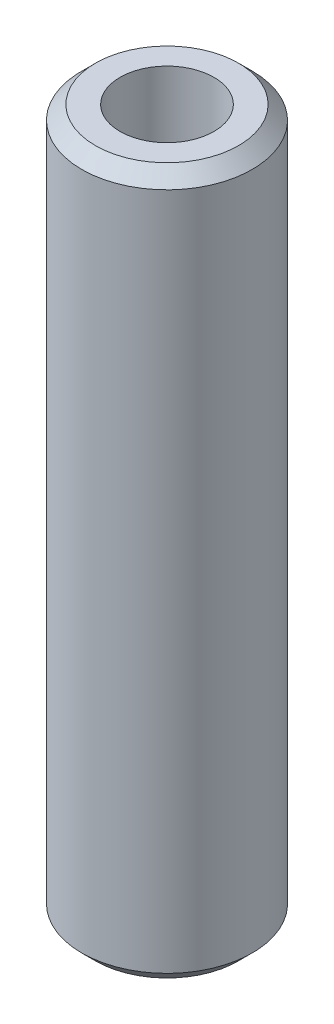
SolidWorks part; units mm, degrees
ref_plane "Front Plane" through (0, 0, 0) normal (0, 0, 1) x (1, 0, 0)
ref_plane "Top Plane" through (0, 0, 0) normal (0, 1, 0) x (1, 0, 0)
ref_plane "Right Plane" through (0, 0, 0) normal (1, 0, 0) x (0, 0, -1)
sketch "Sketch1" plane through (0, 0, 0) normal (0, 1, 0) x (1, 0, 0)
  circle A0 centre (0, 0) radius 22.5
  dimension "SHAFT_OD" = 45
extrude "Boss-Extrude1" add sketch "Sketch1" along normal blind 186.3393
sketch "Sketch2" plane through (0, 0, 0) normal (0, 1, 0) x (1, 0, 0)
  circle A0 centre (0, 0) radius 12.393
  dimension "BORE_D" = 24.786
extrude "Cut-Extrude1" cut sketch "Sketch2" along normal through all
chamfer "Chamfer1" distance 3.6251 angle 45 2 edges at (0, 186.3393, 22.5) (0, 0, 22.5)
